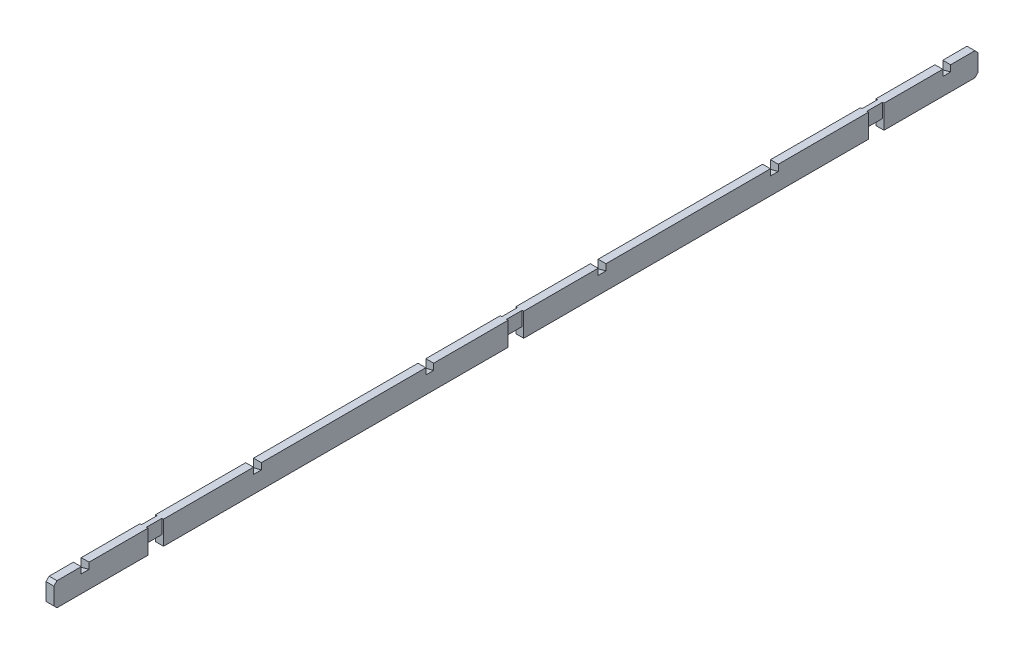
SolidWorks part; units mm, degrees
ref_plane "Front" through (0, 0, 0) normal (0, 0, 1) x (1, 0, 0)
ref_plane "Top" through (0, 0, 0) normal (0, 1, 0) x (1, 0, 0)
ref_plane "Right" through (0, 0, 0) normal (1, 0, 0) x (0, 0, -1)
sketch "Esquisse1" plane through (0, 0, 0) normal (0, 0, 1) x (1, 0, 0)
  line L1 (0, 0) -> (50, 0)
  line L2 (0, 0) -> (0, 150)
  line L3 (0, 150) -> (50, 150)
  line L4 (50, 0) -> (50, 150)
  dimension "D1" = 50
  dimension "D2" = 150
extrude "Boss.-Extru.1" add sketch "Esquisse1" along normal blind 5900
sketch "Esquisse2" plane through (0, 0, 5900) normal (0, 0, 1) x (1, 0, 0)
  line L0 (0, 96.6025) -> (50, 110)
  line L1 (0, 150) -> (0, 0) construction
  line L2 (50, 0) -> (50, 150) construction
  line L3 (50, 110) -> (50, 150)
  line L4 (50, 150) -> (0, 150)
  line L5 (0, 150) -> (0, 96.6025)
  dimension "D1" = 40
  dimension "D2" = 75
extrude "Enlèv. mat.-Extru.1" cut sketch "Esquisse2" against normal blind 50 from offset 175 offset against normal yes
pattern_linear "Répétition linéaire1" count 6 spacing 1100 along (0, 0, -1) of "Enlèv. mat.-Extru.1"
chamfer "Chanfrein1" distance 20 angle 45 4 edges at (25, 0, 5900) (25, 150, 5900) (25, 0, 0) (25, 150, 0)
sketch "Esquisse3" plane through (0, 0, 0) normal (-1, 0, 0) x (0, 0, 1)
  line L0 (2950, 0) -> (2950, 150) construction
  line L1 (5880, 0) -> (20, 0) construction
  line L2 (3475, 150) -> (2425, 150) construction
  line L3 (1275, 150) -> (225, 150) construction
  line L4 (600, 150) -> (700, 150)
  line L5 (600, 150) -> (600, 0)
  line L6 (600, 0) -> (700, 0)
  line L7 (700, 150) -> (700, 0)
  line L8 (3000, 150) -> (2900, 150)
  line L9 (2900, 150) -> (2900, 0)
  line L10 (2900, 0) -> (3000, 0)
  line L11 (3000, 150) -> (3000, 0)
  line L12 (5200, 150) -> (5200, 0)
  line L13 (5300, 0) -> (5200, 0)
  line L14 (5300, 150) -> (5300, 0)
  line L15 (5300, 150) -> (5200, 150)
  dimension "D1" = 100
  dimension "D2" = 2300
extrude "Enlèv. mat.-Extru.2" cut sketch "Esquisse3" against normal blind 10
extrude "Enlèv. mat.-Extru.3" cut sketch "Esquisse3<2>" along normal blind 10 from vertex starting at point (50, 150, 20)
sketch "Esquisse3<2>" plane through (0, 0, 0) normal (-1, 0, 0) x (0, 0, 1) same geometry as "Esquisse3"
sketch "Esquisse4" plane through (10, 0, 0) normal (-1, 0, 0) x (0, 0, 1)
  line L0 (700, 0) -> (700, 150) construction
  line L1 (600, 0) -> (700, 0)
  line L2 (600, 0) -> (600, 60)
  line L3 (600, 60) -> (700, 60)
  line L4 (700, 0) -> (700, 60)
  line L5 (3000, 0) -> (3000, 150) construction
  line L6 (2900, 0) -> (3000, 0)
  line L7 (2900, 0) -> (2900, 60)
  line L8 (2900, 60) -> (3000, 60)
  line L9 (3000, 0) -> (3000, 60)
  line L10 (5300, 0) -> (5300, 150) construction
  line L11 (5200, 0) -> (5300, 0)
  line L12 (5200, 0) -> (5200, 60)
  line L13 (5200, 60) -> (5300, 60)
  line L14 (5300, 0) -> (5300, 60)
  dimension "D1" = 60
extrude "Enlèv. mat.-Extru.4" cut sketch "Esquisse4" against normal through all
